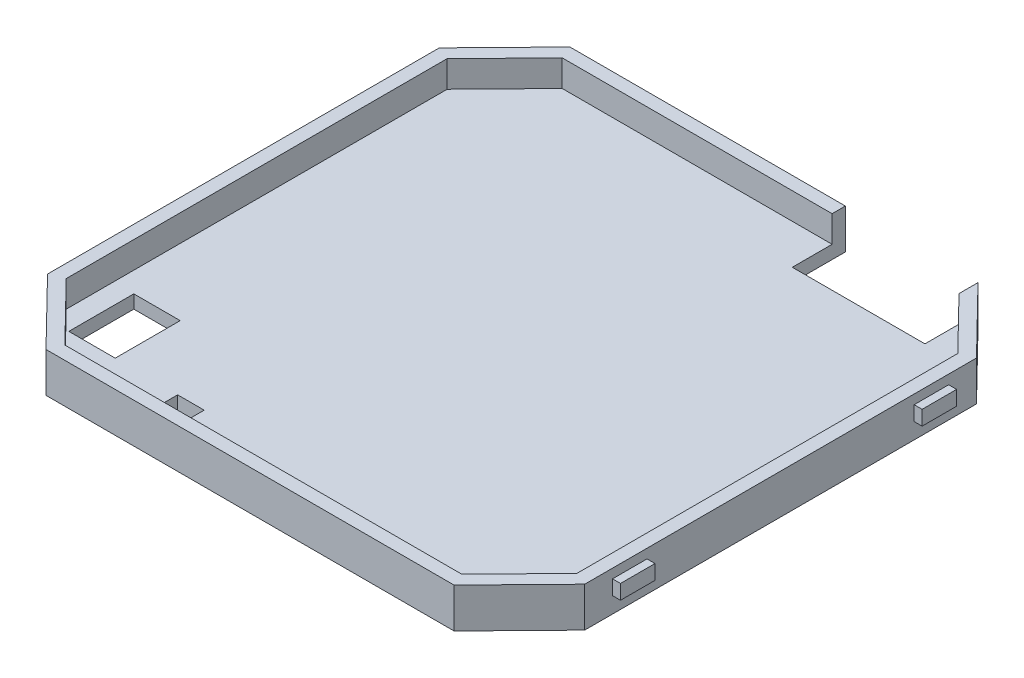
SolidWorks part; units mm, degrees
ref_plane "Front Plane" through (0, 0, 0) normal (0, 0, 1) x (1, 0, 0)
ref_plane "Top Plane" through (0, 0, 0) normal (0, 1, 0) x (1, 0, 0)
ref_plane "Right Plane" through (0, 0, 0) normal (1, 0, 0) x (0, 0, -1)
sketch "Sketch1" plane through (0, 0, 0) normal (0, 1, 0) x (1, 0, 0)
  line L0 (-21.5541, 21.1184) -> (21.4459, 21.1184) construction
  line L1 (-21.5541, -20.8816) -> (21.4459, -20.8816) construction
  line L2 (21.4459, 21.1184) -> (21.4459, -20.8816) construction
  line L3 (21.4459, -20.8816) -> (-21.5541, 21.1184) construction
  line L4 (21.4459, 21.1184) -> (-21.5541, -20.8816) construction
  line L5 (-21.5541, 21.1184) -> (-21.5541, -20.8816) construction
  line L6 (-21.5541, 15.3954) -> (-15.9641, 21.1184)
  line L7 (-21.5541, -15.1586) -> (-15.9641, -20.8816)
  line L8 (21.4459, -15.1586) -> (15.856, -20.8816)
  line L9 (21.4459, 15.3954) -> (15.856, 21.1184)
  line L10 (21.4459, -15.1586) -> (21.4459, 15.3954)
  line L11 (15.856, -20.8816) -> (-15.9641, -20.8816)
  line L12 (-15.9641, 21.1184) -> (15.856, 21.1184)
  line L13 (-21.5541, 15.3954) -> (-21.5541, -15.1586)
  line L14 (-20.3041, 14.8862) -> (-20.3041, -14.6495)
  line L15 (-20.3041, -14.6495) -> (-15.4377, -19.6316)
  line L16 (15.3296, -19.6316) -> (-15.4377, -19.6316)
  line L17 (20.1959, -14.6495) -> (15.3296, -19.6316)
  line L18 (20.1959, -14.6495) -> (20.1959, 14.8862)
  line L19 (20.1959, 14.8862) -> (15.3296, 19.8684)
  line L20 (-15.4377, 19.8684) -> (15.3296, 19.8684)
  line L21 (-20.3041, 14.8862) -> (-15.4377, 19.8684)
  line L22 (-19.3041, 14.4788) -> (-15.0166, 18.8684)
  line L23 (-15.0166, 18.8684) -> (14.9085, 18.8684)
  line L24 (19.1959, 14.4788) -> (14.9085, 18.8684)
  line L25 (19.1959, -14.2421) -> (19.1959, 14.4788)
  line L26 (19.1959, -14.2421) -> (14.9085, -18.6316)
  line L27 (14.9085, -18.6316) -> (-15.0166, -18.6316)
  line L28 (-19.3041, -14.2421) -> (-15.0166, -18.6316)
  line L29 (-19.3041, 14.4788) -> (-19.3041, -14.2421)
  line L35 (-17.759, -10.6898) -> (-14.2619, -10.6898)
  line L36 (-17.759, -10.6898) -> (-17.759, -15.5898)
  line L37 (-17.759, -15.5898) -> (-14.2619, -15.5898)
  line L38 (-14.2619, -10.6898) -> (-14.2619, -15.5898)
  line L39 (-17.759, -10.6898) -> (-14.2619, -15.5898) construction
  line L40 (-17.759, -15.5898) -> (-14.2619, -10.6898) construction
  line L41 (-9.512, -15.6316) -> (-7.512, -15.6316)
  line L42 (-9.512, -15.6316) -> (-9.512, -18.6316)
  line L43 (-9.512, -18.6316) -> (-7.512, -18.6316)
  line L44 (-7.512, -15.6316) -> (-7.512, -18.6316)
  line L45 (-9.512, -15.6316) -> (-7.512, -18.6316) construction
  line L46 (-9.512, -18.6316) -> (-7.512, -15.6316) construction
  line L51 (15.3296, 19.8684) -> (5.3296, 19.8684)
  line L52 (15.3296, 19.8684) -> (15.3296, 15.8684)
  line L53 (15.3296, 15.8684) -> (5.3296, 15.8684)
  line L54 (5.3296, 19.8684) -> (5.3296, 15.8684)
  point P5 (-0.0541, 0.1184)
  point P29 (-16.0104, -13.1398)
  point P34 (-8.512, -17.1316)
  point P39 (0, 0)
  point P40 (0, 0)
  point P42 (15.3059, 19.8684)
  dimension "D1" = 42
  dimension "D2" = 43
  dimension "D3" = 8
  dimension "D4" = 8
  dimension "D5" = 8
  dimension "D6" = 8
  dimension "D9" = 10
  dimension "D10" = 4
  dimension "D11" = 3.497
  dimension "D12" = 4.9
  dimension "D13" = 2
  dimension "D14" = 3
  dimension "D7" = 1.25
  dimension "D8" = 1
extrude "Boss-Extrude1" add sketch "Sketch1" along normal blind 1 contours L14 L15 L16 L17 L18 L19 L20 L21
extrude "Boss-Extrude2" add sketch "Sketch1<3>" along normal blind 2 from surface contours L29 L28 L27 L26 L25 L24 L23 L22 | L14 L15 L16 L17 L18 L19 L20 L21 starting at face at (-0.0541, 1, -0.1184)
sketch "Sketch1<3>" plane through (0, 0, 0) normal (0, 1, 0) x (1, 0, 0) same geometry as "Sketch1"
extrude "Cut-Extrude1" cut sketch "Sketch1<4>" against normal through all both and the other way through all from surface contours L44 L41 L42 L43 | L38 L35 L36 L37 | L52 L51 L54 L53 region at (-8.512, 0, 17.1316) region at (-16.0104, 0, 13.1398) starting at face at (-0.0541, 1, -0.1184)
sketch "Sketch1<4>" plane through (0, 0, 0) normal (0, 1, 0) x (1, 0, 0) same geometry as "Sketch1"
sketch "Sketch2" plane through (0, 0, 0) normal (1, 0, 0) x (0, 0, -1)
  line L0 (-9.9513, 1.2) -> (-9.9513, 2.3)
  line L1 (-9.7513, 1) -> (-12.7513, 1) construction
  line L2 (-9.7513, 1) -> (-9.7513, 2.5) construction
  line L3 (-9.7513, 2.5) -> (-12.7513, 2.5) construction
  line L4 (-12.7513, 1) -> (-12.7513, 2.5) construction
  line L5 (-9.9513, 2.3) -> (-12.5513, 2.3)
  line L6 (-12.5513, 1.2) -> (-12.5513, 2.3)
  line L7 (-9.9513, 1.2) -> (-12.5513, 1.2)
  line L8 (12.788, 1.2) -> (10.188, 1.2)
  line L9 (12.988, 1) -> (9.988, 1) construction
  line L10 (12.988, 1) -> (12.988, 2.5) construction
  line L11 (12.988, 2.5) -> (9.988, 2.5) construction
  line L12 (9.988, 1) -> (9.988, 2.5) construction
  line L13 (10.188, 1.2) -> (10.188, 2.3)
  line L14 (12.788, 2.3) -> (10.188, 2.3)
  line L15 (12.788, 1.2) -> (12.788, 2.3)
  dimension "D1" = 0.2
  dimension "D2" = 0.2
extrude "Boss-Extrude3" add sketch "Sketch2" against normal blind 0.6 from surface starting at face at (-20.3041, 1.5, -0.1184)
extrude "Boss-Extrude4" add sketch "Sketch2<2>" along normal blind 0.6 from surface starting at face at (20.1959, 1.5, -0.1184)
sketch "Sketch2<2>" plane through (0, 0, 0) normal (1, 0, 0) x (0, 0, -1) same geometry as "Sketch2"
